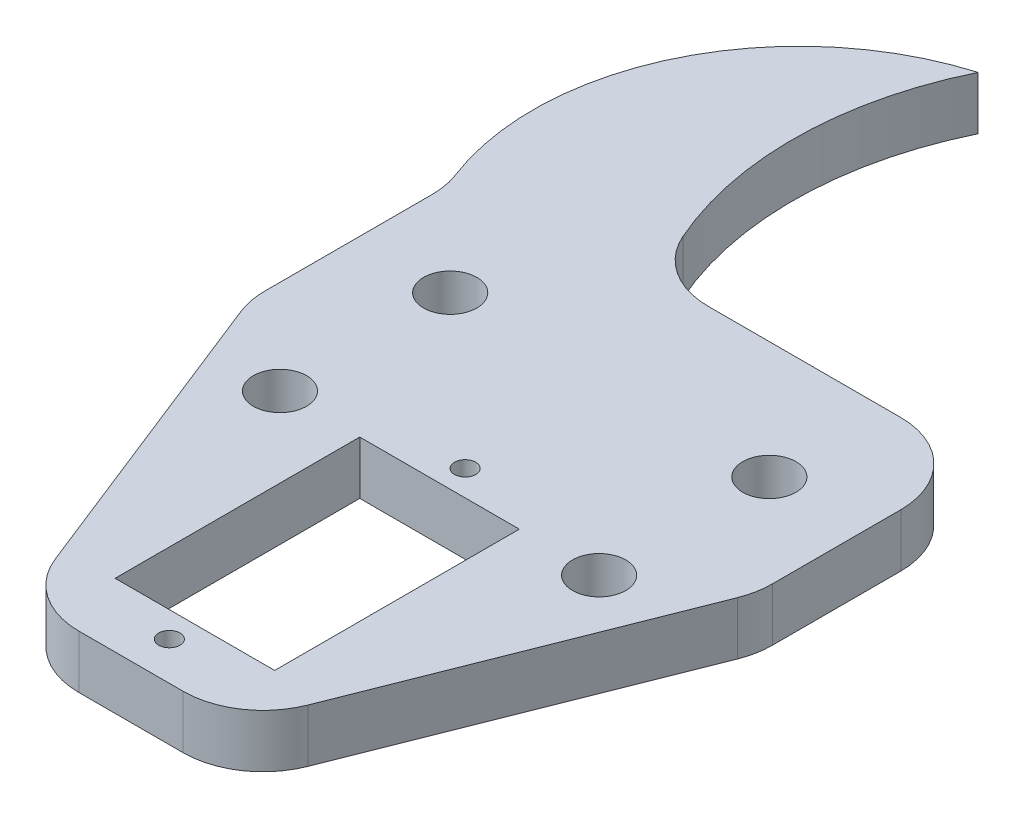
SolidWorks part; units mm, degrees
ref_plane "Front Plane" through (0, 0, 0) normal (0, 0, 1) x (1, 0, 0)
ref_plane "Top Plane" through (0, 0, 0) normal (0, 1, 0) x (1, 0, 0)
ref_plane "Right Plane" through (0, 0, 0) normal (1, 0, 0) x (0, 0, -1)
sketch "Sketch1" plane through (0, 0, 0) normal (0, 1, 0) x (1, 0, 0)
  line L0 (0, 0) -> (0, 25) construction
  circle A0 centre (0, 0) radius 25
  dimension "D1" = 50
extrude "Boss-Extrude1" add sketch "Sketch1" along normal blind 5 contours A0
sketch "Sketch2" plane through (0, 5, 0) normal (0, 1, 0) x (1, 0, 0)
  circle A1 centre (0, 0) radius 25
  arc A2 (-7.1336, 23.9606) -> (12.987, -21.3621) centre (22.0649, 9.7955) ccw
  circle A3 centre (0, 0) radius 25 construction
  circle M1 centre (0, 0) radius 25
extrude "Cut-Extrude1" cut sketch "Sketch2" against normal blind 5 contours A2 M1 region at (7.1803, 5, -3.1876)
sketch "Sketch4" plane through (0, 5, 0) normal (0, 1, 0) x (1, 0, 0)
  line L5 (-5.2277, -7.7634) -> (24.8405, -7.7634)
  line L6 (24.8405, -7.7634) -> (24.8405, -28.7824)
  line L7 (24.8405, -28.7824) -> (-22.8496, -28.7824)
  line L8 (-22.8496, -28.7824) -> (-22.8496, -10.1439)
  arc A0 (-7.1336, 23.9606) -> (12.987, -21.3621) centre (22.0649, 9.7955) ccw construction
  arc A3 (-7.1336, 23.9606) -> (12.987, -21.3621) centre (0, 0) ccw construction
  arc A5 (-7.1336, 23.9606) -> (12.987, -21.3621) centre (22.0649, 9.7955) ccw
  arc A8 (-7.1336, 23.9606) -> (12.987, -21.3621) centre (0, 0) ccw
  arc A9 (-7.1336, 23.9606) -> (12.987, -21.3621) centre (22.0649, 9.7955) ccw
  arc A10 (-7.1336, 23.9606) -> (12.987, -21.3621) centre (0, 0) ccw
  arc M8 (12.987, -21.3621) -> (-7.1336, 23.9606) centre (22.0649, 9.7955) cw
  arc M9 (-7.1336, 23.9606) -> (12.987, -21.3621) centre (0, 0) ccw
  dimension "D4" = 0
extrude "Boss-Extrude2" add sketch "Sketch4" against normal blind 5 contours L8 L7 L6 L5 M8 M9 region at (9.8064, 5, 8.2846)
sketch "Sketch7" plane through (0, 5, 0) normal (0, 1, 0) x (1, 0, 0)
  line L0 (0.9955, -28.7824) -> (0.9955, -46.2824) construction
  line L1 (24.8405, -28.7824) -> (-22.8496, -28.7824) construction
  line L2 (0.9955, -46.2824) -> (0.9955, -60.1824) construction
  line L3 (-9.0045, -63.7824) -> (10.9955, -63.7824)
  line L4 (-9.0045, -63.7824) -> (-9.0045, -28.7824)
  line L5 (-9.0045, -28.7824) -> (10.9955, -28.7824)
  line L6 (10.9955, -63.7824) -> (10.9955, -28.7824)
  line L7 (-9.0045, -63.7824) -> (10.9955, -28.7824) construction
  line L8 (-9.0045, -28.7824) -> (10.9955, -63.7824) construction
  line L9 (-6.5045, -57.7824) -> (8.4955, -57.7824)
  line L10 (-6.5045, -57.7824) -> (-6.5045, -34.7824)
  line L11 (-6.5045, -34.7824) -> (8.4955, -34.7824)
  line L12 (8.4955, -57.7824) -> (8.4955, -34.7824)
  line L13 (-6.5045, -57.7824) -> (8.4955, -34.7824) construction
  line L14 (-6.5045, -34.7824) -> (8.4955, -57.7824) construction
  line L15 (0.9955, -46.2824) -> (10.9955, -46.2824) construction
  circle A0 centre (0.9955, -60.1824) radius 1
  circle A1 centre (0.9955, -32.3824) radius 1
  dimension "D7" = 2
  dimension "D1" = 17.5
  dimension "D2" = 35
  dimension "D3" = 20
  dimension "D4" = 15
  dimension "D5" = 23
  dimension "D6" = 13.9
extrude "Boss-Extrude3" add sketch "Sketch7" against normal blind 5
sketch "Sketch9" plane through (0, 5, 0) normal (0, 1, 0) x (1, 0, 0)
  line L0 (-22.8496, -28.7824) -> (-9.0045, -63.7824)
  line L1 (-9.0045, -63.7824) -> (10.9955, -63.7824)
  line L2 (10.9955, -63.7824) -> (24.8405, -28.7824)
  line L3 (24.8405, -28.7824) -> (-22.8496, -28.7824)
  line L20 (-22.8496, -10.1439) -> (-22.8496, -28.7824)
  line L21 (-22.8496, -28.7824) -> (-9.0045, -28.7824)
  line L22 (-9.0045, -28.7824) -> (-9.0045, -63.7824)
  line L23 (-9.0045, -63.7824) -> (10.9955, -63.7824)
  line L24 (10.9955, -63.7824) -> (10.9955, -28.7824)
  line L25 (10.9955, -28.7824) -> (24.8405, -28.7824)
  line L26 (24.8405, -28.7824) -> (24.8405, -7.7634)
  line L27 (24.8405, -7.7634) -> (-5.2277, -7.7634)
  line L28 (-22.8496, -10.1439) -> (-22.8496, -28.7824)
  line L29 (-22.8496, -28.7824) -> (-9.0045, -28.7824)
  line L30 (-9.0045, -28.7824) -> (-9.0045, -63.7824)
  line L31 (-9.0045, -63.7824) -> (10.9955, -63.7824)
  line L32 (10.9955, -63.7824) -> (10.9955, -28.7824)
  line L33 (10.9955, -28.7824) -> (24.8405, -28.7824)
  line L34 (24.8405, -28.7824) -> (24.8405, -7.7634)
  line L35 (24.8405, -7.7634) -> (-5.2277, -7.7634)
  arc A4 (-7.1336, 23.9606) -> (-5.2277, -7.7634) centre (22.0649, 9.7955) ccw
  arc A5 (-7.1336, 23.9606) -> (-22.8496, -10.1439) centre (0, 0) ccw
  arc A6 (-7.1336, 23.9606) -> (-5.2277, -7.7634) centre (22.0649, 9.7955) ccw
  arc A7 (-7.1336, 23.9606) -> (-22.8496, -10.1439) centre (0, 0) ccw
  line M16 (-22.8496, -28.7824) -> (-9.0045, -28.7824)
  line M17 (-9.0045, -28.7824) -> (-9.0045, -63.7824)
  line M19 (10.9955, -63.7824) -> (10.9955, -28.7824)
  line M20 (10.9955, -28.7824) -> (24.8405, -28.7824)
  dimension "D1" = 0
extrude "Boss-Extrude4" add sketch "Sketch9" against normal blind 5 contours L0 M16 M17 | L2 M19 M20 region at (-13.6195, 5, 40.4491) region at (15.6105, 5, 40.4491)
sketch "Sketch10" plane through (0, 5, 0) normal (0, 1, 0) x (1, 0, 0)
  line L0 (0.9955, -57.7824) -> (0.9955, -34.7824) construction
  line L1 (-6.5045, -57.7824) -> (8.4955, -57.7824) construction
  line L2 (8.4955, -34.7824) -> (-6.5045, -34.7824) construction
  line L3 (0.9955, -34.7824) -> (15.9955, -34.7824) construction
  line L4 (0.9955, -63.7824) -> (0.9955, -26.7824) construction
  line L5 (-9.0045, -63.7824) -> (10.9955, -63.7824) construction
  line L6 (0.9955, -26.7824) -> (24.8405, -26.7824) construction
  line L7 (24.8405, -7.7634) -> (24.8405, -28.7824) construction
  line L8 (15.9955, -18.7824) -> (24.8405, -18.7824) construction
  line L9 (-14.0045, -18.7824) -> (-22.8496, -18.7824) construction
  line L10 (-22.8496, -28.7824) -> (-22.8496, -10.1439) construction
  circle A0 centre (15.9955, -34.7824) radius 2.5
  circle A1 centre (-14.0045, -34.7824) radius 2.5
  circle A2 centre (15.9955, -18.7824) radius 2.5
  circle A3 centre (-14.0045, -18.7824) radius 2.5
  dimension "D1" = 5
  dimension "D2" = 15
  dimension "D3" = 37
extrude "Cut-Extrude3" cut sketch "Sketch10" against normal blind 5
fillet "Fillet3" radius 7.5 7 edges at (-22.8496, 2.5, 10.1439) (-22.8496, 2.5, 28.7824) (10.9955, 2.5, 63.7824) (-9.0045, 2.5, 63.7824) (24.8405, 2.5, 28.7824) (24.8405, 2.5, 7.7634) (-5.2277, 2.5, 7.7634)
ref_axis "Axis1" through (15.9955, 0, 18.7824) along (0, 1, 0)
